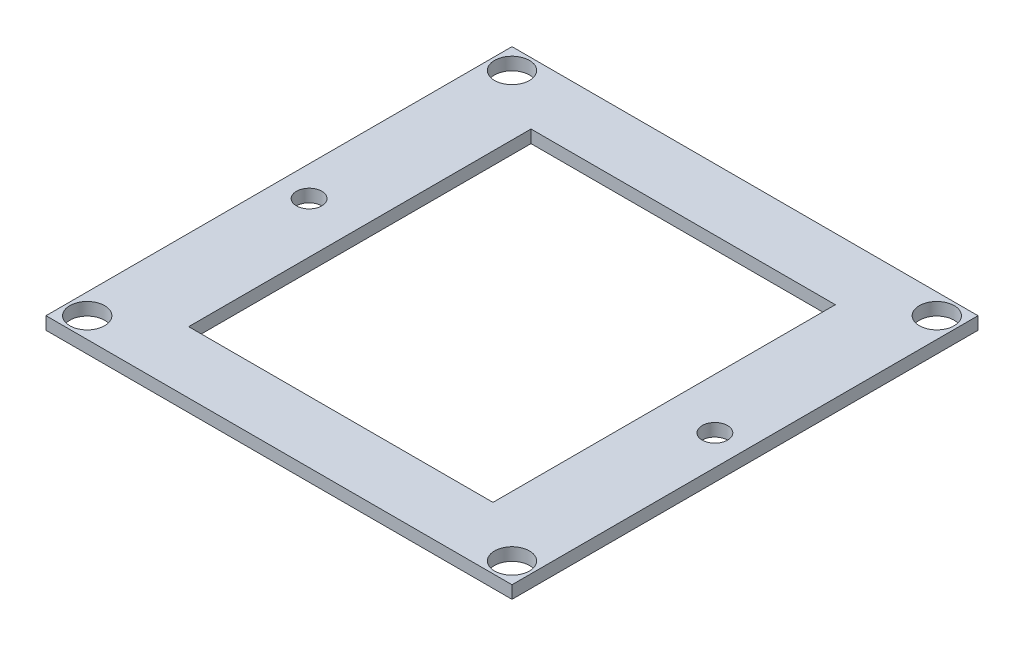
SolidWorks part; units mm, degrees
ref_plane "Front Plane" through (0, 0, 0) normal (0, 0, 1) x (1, 0, 0)
ref_plane "Top Plane" through (0, 0, 0) normal (0, 1, 0) x (1, 0, 0)
ref_plane "Right Plane" through (0, 0, 0) normal (1, 0, 0) x (0, 0, -1)
sketch "Sketch1" plane through (0, 0, 0) normal (0, 1, 0) x (1, 0, 0)
  line L0 (147, 147) -> (147, -147)
  line L1 (-147, -147) -> (147, -147)
  line L2 (-147, -147) -> (-147, 147)
  line L3 (-147, 147) -> (147, 147)
  line L5 (-147, -147) -> (147, 147) construction
  line L6 (-147, 147) -> (147, -147) construction
  line L7 (-96, -108) -> (96, -108)
  line L8 (-96, -108) -> (-96, 108)
  line L9 (-96, 108) -> (96, 108)
  line L10 (96, -108) -> (96, 108)
  line L11 (-96, -108) -> (96, 108) construction
  line L12 (-96, 108) -> (96, -108) construction
  point P0 (0, 0)
  point P5 (0, 0)
  dimension "D1" = 294
  dimension "D2" = 192
  dimension "D3" = 216
extrude "Boss-Extrude1" add sketch "Sketch1" along normal blind 8
sketch "Sketch2" plane through (0, 0, 0) normal (0, 1, 0) x (1, 0, 0)
  line L1 (147, 147) -> (-147, 147) construction
  line L2 (147, -147) -> (147, 147) construction
  circle A0 centre (134, 134) radius 11
  dimension "D1" = 22
  dimension "D2" = 13
  dimension "D3" = 13
extrude "Cut-Extrude1" cut sketch "Sketch2" along normal through all
sketch "Sketch4" plane through (0, 8, 0) normal (0, 1, 0) x (1, 0, 0)
  line L0 (134, -864) -> (134, 49136) construction
  circle A0 centre (128, 0) radius 8
  dimension "D1" = 6
  dimension "D2" = 16
mirror "Mirror2" about plane through (0, 0, 0) normal (0, 0, 1) of "Cut-Extrude1"
extrude "Cut-Extrude2" cut sketch "Sketch4" against normal through all
mirror "Mirror3" about plane through (0, 0, 0) normal (1, 0, 0) of "Mirror2", "Cut-Extrude1"
mirror "Mirror4" about plane through (0, 0, 0) normal (1, 0, 0) of "Cut-Extrude2"
